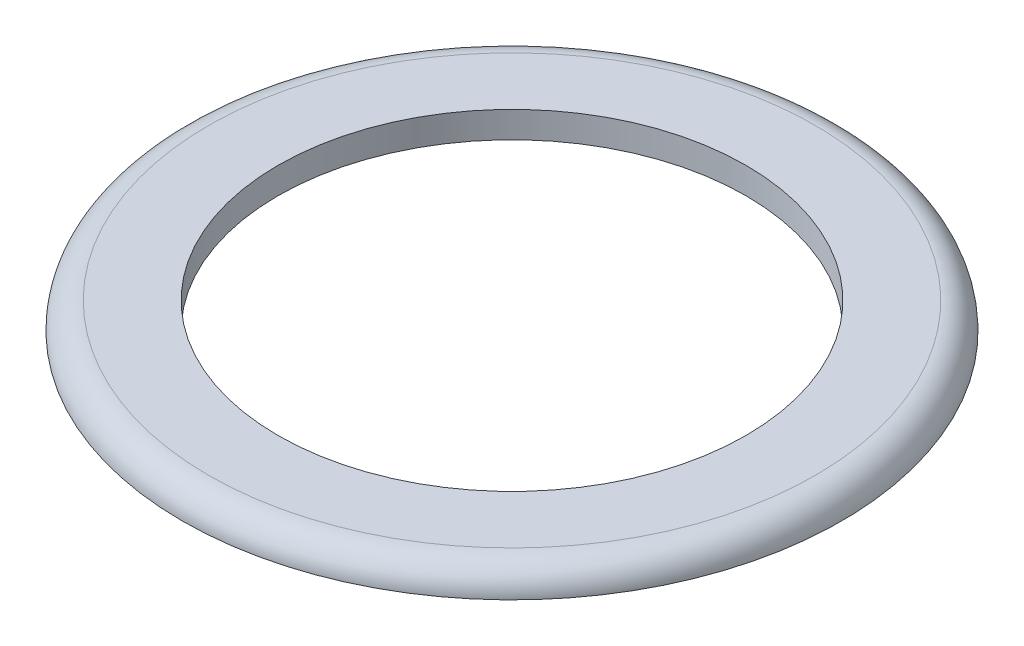
SolidWorks part; units mm, degrees
ref_plane "Front Plane" through (0, 0, 0) normal (0, 0, 1) x (1, 0, 0)
ref_plane "Top Plane" through (0, 0, 0) normal (0, 1, 0) x (1, 0, 0)
ref_plane "Right Plane" through (0, 0, 0) normal (1, 0, 0) x (0, 0, -1)
sketch "Sketch1" plane through (0, 0, 0) normal (0, 1, 0) x (1, 0, 0)
  circle A0 centre (0, 0) radius 17.75
  circle A1 centre (0, 0) radius 25
  dimension "D1" = 35.5
  dimension "D2" = 50
extrude "Boss-Extrude1" add sketch "Sketch1" along normal blind 2
fillet "Fillet1" radius 2 1 edges at (0, 2, 25)
